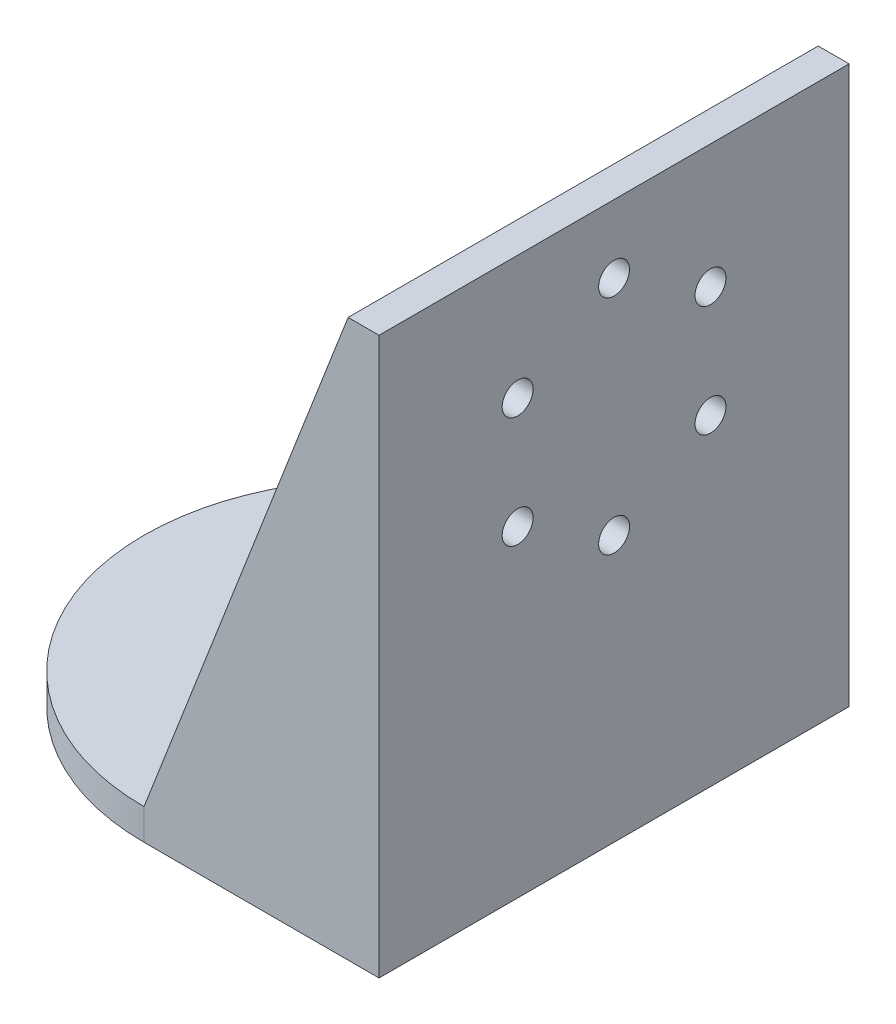
SolidWorks part; units mm, degrees
ref_plane "Спереди" through (0, 0, 0) normal (0, 0, 1) x (1, 0, 0)
ref_plane "Сверху" through (0, 0, 0) normal (0, 1, 0) x (1, 0, 0)
ref_plane "Справа" through (0, 0, 0) normal (1, 0, 0) x (0, 0, -1)
sketch "Эскиз3" plane through (0, 0, 0) normal (0, 0, 1) x (1, 0, 0)
  line L1 (76, 0) -> (0, 0)
  line L3 (71, 5) -> (0, 5)
  line L4 (0, 0) -> (0, 5)
  line L8 (76, 0) -> (76, 90)
  line L9 (76, 90) -> (71, 90)
  line L10 (71, 5) -> (71, 90)
  point P0 (0, 0)
  dimension "D1" = 5
  dimension "D2" = 76
  dimension "D3" = 5
  dimension "D4" = 90
extrude "Бобышка-Вытянуть1" add sketch "Эскиз3" along normal blind 76
fillet "Скругление1" radius 38 2 edges at (0, 2.5, 0) (0, 2.5, 76)
ref_plane "Плоскость7" through (0, 0, 0) normal (0, 0, -1) x (-1, 0, 0)
ref_plane "Плоскость8" through (0, 0, 76) normal (0, 0, 1) x (1, 0, 0)
sketch "Эскиз4" plane through (0, 0, 76) normal (0, 0, 1) x (1, 0, 0)
  line L0 (71, 90) -> (38, 5)
rib "Ребро1" sketch "Эскиз4" sketch "Эскиз4" thickness 5 extrusion direction parallel to sketch draft on no parameters "D1"=5
sketch "Эскиз5" plane through (0, 0, 0) normal (0, 0, -1) x (-1, 0, 0)
  line L0 (-71, 90) -> (-38, 5)
rib "Ребро2" sketch "Эскиз5" sketch "Эскиз5" thickness 5 extrusion direction parallel to sketch draft on no parameters "D1"=5
sketch "Эскиз7" plane through (0, 5, 0) normal (0, 1, 0) x (1, 0, 0)
  line L0 (38, -38) -> (20, -38) construction
  circle A0 centre (38, -38) radius 18 construction
  circle A1 centre (20, -38) radius 2.5
  circle A2 centre (38, -38) radius 18
  circle A3 centre (29, -22.4115) radius 2.5
  circle A4 centre (38, -38) radius 18
  circle A5 centre (47, -22.4115) radius 2.5
  circle A6 centre (38, -38) radius 18
  circle A7 centre (56, -38) radius 2.5
  circle A8 centre (38, -38) radius 18
  circle A9 centre (47, -53.5885) radius 2.5
  circle A10 centre (38, -38) radius 18
  circle A11 centre (29, -53.5885) radius 2.5
  dimension "D1" = 36
  dimension "D2" = 5
  dimension "D3" = 6
extrude "Вырез-Вытянуть1" cut sketch "Эскиз7" against normal blind 10 contours A1 | A3 | A5 | A7 | A9 | A11
sketch "Эскиз8" plane through (76, 0, 0) normal (1, 0, 0) x (0, 0, -1)
  line L0 (-76, 0) -> (0, 0) construction
  line L1 (0, 0) -> (0, 90) construction
  line L2 (-38, 61) -> (-38, 43) construction
  circle A0 centre (-38, 61) radius 18 construction
  circle A1 centre (-38, 43) radius 2.5
  circle A2 centre (-38, 61) radius 18
  circle A3 centre (-53.5885, 52) radius 2.5
  circle A4 centre (-38, 61) radius 18
  circle A5 centre (-53.5885, 70) radius 2.5
  circle A6 centre (-38, 61) radius 18
  circle A7 centre (-38, 79) radius 2.5
  circle A8 centre (-38, 61) radius 18
  circle A9 centre (-22.4115, 70) radius 2.5
  circle A10 centre (-38, 61) radius 18
  circle A11 centre (-22.4115, 52) radius 2.5
  dimension "D1" = 36
  dimension "D2" = 61
  dimension "D4" = 5
  dimension "D3" = 38
  dimension "D5" = 6
extrude "Вырез-Вытянуть2" cut sketch "Эскиз8" against normal blind 10 contours A5 | A7 | A9 | A11 | A1 | A3
